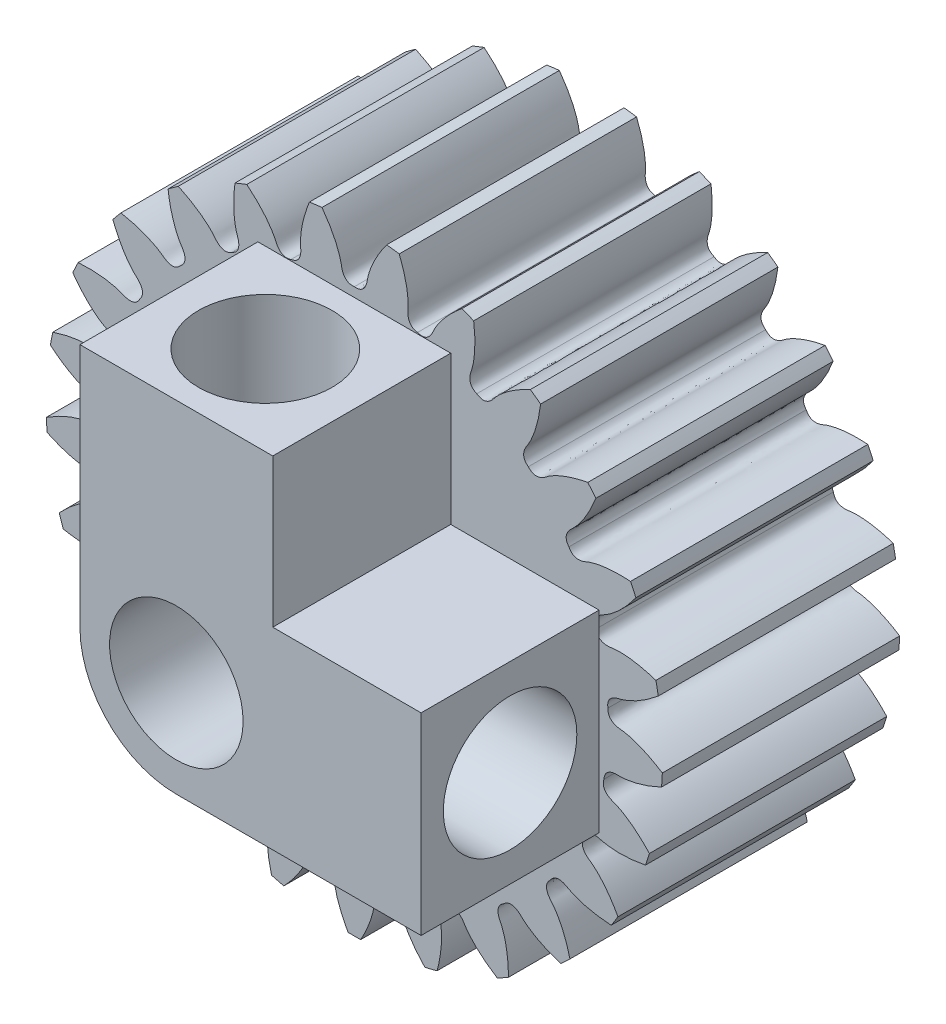
SolidWorks part; units mm, degrees
material "PLA Black"
ref_plane "Front" through (0, 0, 0) normal (0, 0, 1) x (1, 0, 0)
ref_plane "Top" through (0, 0, 0) normal (0, 1, 0) x (1, 0, 0)
ref_plane "Right" through (0, 0, 0) normal (1, 0, 0) x (0, 0, -1)
ref_axis "Axis1" through (0, 0, -15.6032) along (0, 0, 1)
sketch "Gear-BaseSketch" plane through (0, 0, 0) normal (0, 0, 1) x (1, 0, 0)
  circle A0 centre (0, 0) radius 10.3909
  dimension "D1" = 20.7818
extrude "33.0 Diametral Pitch, 20.78mm P.D." add sketch "Gear-BaseSketch" along normal mid plane 8
sketch "Tooth-Sketch; Backlash: 0.0000mm" plane through (0, 0, 0) normal (0, 0, 1) x (1, 0, 0)
  line L0 (0, 0) -> (0, 10.3909) construction
  arc A0 (-1.0905, 10.334) -> (1.0905, 10.334) centre (0, -0.094) cw
  circle A1 centre (0, 0) radius 10.3909 construction
  spline S0 degree 3 poles (-1.0905, 10.334) (-1.0138, 10.2299) (-0.9082, 10.0753) (-0.7851, 9.8689) (-0.7088, 9.729) (-0.6442, 9.5985) (-0.5903, 9.4783) (-0.5464, 9.369) (-0.5115, 9.2711) (-0.4845, 9.1851) (-0.4645, 9.1115) (-0.4506, 9.0507) (-0.4416, 9.0039) (-0.4365, 8.9698) (-0.432, 8.9444) (-0.4246, 8.9083) (-0.4122, 8.8596) (-0.3912, 8.7995) (-0.3638, 8.742) (-0.3272, 8.686) (-0.2761, 8.6321) (-0.1724, 8.5642) (-0.0681, 8.5594) (0, 8.5647) knots 0 0 0 0 0.176711 0.2556 0.328177 0.394444 0.454399 0.508044 0.555377 0.596399 0.63111 0.65951 0.681599 0.696189 0.706616 0.716848 0.746535 0.775185 0.80367 0.83335 0.866218 0.904587 1 1 1 1
  spline S1 degree 3 poles (1.0905, 10.334) (1.0138, 10.2299) (0.9082, 10.0753) (0.7851, 9.8689) (0.7088, 9.729) (0.6442, 9.5985) (0.5903, 9.4783) (0.5464, 9.369) (0.5115, 9.2711) (0.4845, 9.1851) (0.4645, 9.1115) (0.4506, 9.0507) (0.4416, 9.0039) (0.4365, 8.9698) (0.432, 8.9444) (0.4246, 8.9083) (0.4122, 8.8596) (0.3912, 8.7995) (0.3638, 8.742) (0.3272, 8.686) (0.2761, 8.6321) (0.1724, 8.5642) (0.0681, 8.5594) (0, 8.5647) knots 0 0 0 0 0.176711 0.2556 0.328177 0.394444 0.454399 0.508044 0.555377 0.596399 0.63111 0.65951 0.681599 0.696189 0.706616 0.716848 0.746535 0.775185 0.80367 0.83335 0.866218 0.904587 1 1 1 1
extrude "Tooth-Cut, Fine Pitch Involute 20 deg" cut sketch "Tooth-Sketch; Backlash: 0.0000mm" against normal through all and the other way through all
pattern_circular "Tooth Pattern, 25 / 25" count 25 over 360 about axis through (0, 0, -15.6032) along (0, 0, 1) of "Tooth-Cut, Fine Pitch Involute 20 deg"
sketch "Sketch4" plane through (0, 0, 4) normal (0, 0, 1) x (1, 0, 0)
  circle A0 centre (0, 0) radius 2.25
  dimension "D1" = 4.5
extrude "Cut-Extrude2" cut sketch "Sketch4" against normal through all contours A0
sketch "Sketch6" plane through (0, 0, 4) normal (0, 0, 1) x (1, 0, 0)
  circle A0 centre (0, 0) radius 3.25
  circle A1 centre (0, 0) radius 2.25
  circle A2 centre (0, 0) radius 2.25 construction
  dimension "D1" = 6.5
extrude "Boss-Extrude2" add sketch "Sketch6" along normal blind 6
sketch "Sketch9" plane through (0, 0, 4) normal (0, 0, 1) x (1, 0, 0)
  line L0 (-3.25, 0) -> (-3.25, 8.25)
  line L1 (-3.25, 8.25) -> (3.25, 8.25)
  line L2 (3.25, 8.25) -> (3.25, 3.25)
  line L3 (3.25, 3.25) -> (8.25, 3.25)
  line L4 (8.25, 3.25) -> (8.25, -3.25)
  line L5 (8.25, -3.25) -> (0, -3.25)
  circle A0 centre (0, 0) radius 3.25 construction
  circle A1 centre (0, 0) radius 3.25 construction
  arc A2 (-3.25, 0) -> (0, -3.25) centre (0, 0) cw
  dimension "D1" = 5
extrude "Boss-Extrude4" add sketch "Sketch9" along normal through all
ref_plane "Plane1" through (0, 3.25, 0) normal (0, 1, 0) x (1, 0, 0)
sketch "Sketch10" plane through (0, 8.25, 0) normal (0, 1, 0) x (1, 0, 0)
  line L0 (-3.25, -7) -> (3.25, -7) construction
  line L1 (-3.25, -10) -> (-3.25, -4) construction
  line L2 (3.25, -10) -> (3.25, -4) construction
  line L3 (0, -4) -> (0, -10) construction
  line L4 (3.25, -10) -> (-3.25, -10) construction
  circle A0 centre (0, -7) radius 2.25
  dimension "D1" = 4.5
extrude "Cut-Extrude3" cut sketch "Sketch10" against normal blind 8
sketch "Sketch11" plane through (8.25, 0, 0) normal (1, 0, 0) x (0, 0, -1)
  line L0 (-7, 3.25) -> (-7, -3.25) construction
  line L1 (-10, 3.25) -> (-4, 3.25) construction
  line L2 (-10, -3.25) -> (-4, -3.25) construction
  line L3 (-10, 0) -> (-4, -0.4033) construction
  line L4 (-10, -3.25) -> (-10, 3.25) construction
  line L7 (-4, -3.25) -> (-4, 2.4434) construction
  circle A0 centre (-7, 0) radius 2.25
  dimension "D1" = 4.5
extrude "Cut-Extrude4" cut sketch "Sketch11" against normal blind 8 contours A0
